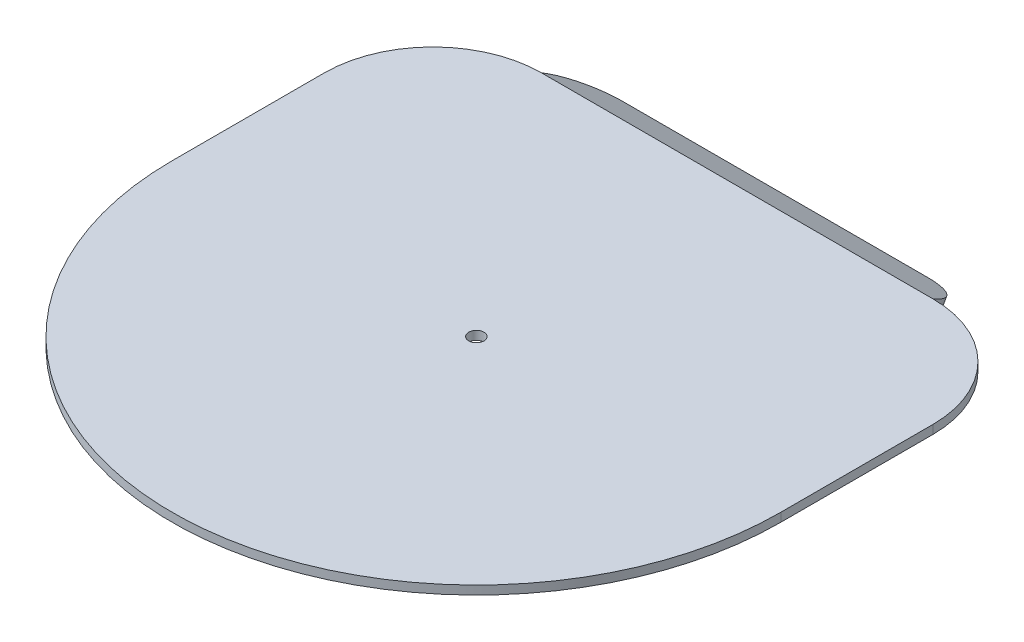
SolidWorks part; units mm, degrees
ref_plane "Front Plane" through (0, 0, 0) normal (0, 0, 1) x (1, 0, 0)
ref_plane "Top Plane" through (0, 0, 0) normal (0, 1, 0) x (1, 0, 0)
ref_plane "Right Plane" through (0, 0, 0) normal (1, 0, 0) x (0, 0, -1)
sketch "Sketch1" plane through (0, 0, 0) normal (0, 1, 0) x (1, 0, 0)
  line L0 (-70, 0) -> (-70, 35)
  line L1 (-45, 60) -> (45, 60)
  line L2 (70, 35) -> (70, 0)
  arc A0 (-70, 0) -> (70, 0) centre (0, 0) ccw
  arc A1 (45, 60) -> (70, 35) centre (45, 35) cw
  arc A2 (-70, 35) -> (-45, 60) centre (-45, 35) cw
  dimension "D1" = 140
  dimension "D3" = 25
  dimension "D2" = 60
extrude "Boss-Extrude1" add sketch "Sketch1" along normal blind 2
sketch "Sketch3" plane through (0, 0, 0) normal (1, 0, 0) x (0, 0, -1)
  line L0 (60, 2) -> (58.8453, 0)
  line L1 (60, 2) -> (68.6603, -3)
  line L2 (58.8453, 0) -> (67.5056, -5)
  line L3 (68.6603, -3) -> (67.5056, -5)
  line L4 (35, 0) -> (60, 0) construction
  line L5 (60, 2) -> (35, 2) construction
  dimension "D1" = 10
  dimension "D2" = 30
extrude "Boss-Extrude2" add sketch "Sketch3" along normal blind 45 and the other way blind 45
fillet "Fillet1" radius 10 2 edges at (-45, -4, -68.0829) (45, -4, -68.0829)
sketch "Sketch4" plane through (0, 2, 0) normal (0, 1, 0) x (1, 0, 0)
  circle A0 centre (0, 0) radius 1.75
  dimension "D1" = 3.5
extrude "Cut-Extrude2" cut sketch "Sketch4" against normal blind 10
sketch "Sketch5" plane through (0, 0, 0) normal (0, -1, 0) x (1, 0, 0)
  circle A0 centre (0, 0) radius 37
  circle A1 centre (0, 0) radius 35
  dimension "D1" = 74
  dimension "D2" = 70
extrude "Boss-Extrude3" add sketch "Sketch5" along normal blind 5
sketch "Sketch6" plane through (0, 0, 0) normal (0, -1, 0) x (1, 0, 0)
  circle A0 centre (0, 0) radius 41
  circle A1 centre (0, 0) radius 43
  dimension "D1" = 82
  dimension "D2" = 86
extrude "Boss-Extrude4" add sketch "Sketch6" along normal blind 5
sketch "Sketch7" plane through (0, 0, 0) normal (0, -1, 0) x (1, 0, 0)
  line L0 (0, -45.4108) -> (0, 0) construction
  line L1 (-4, -49.1795) -> (4, -49.1795)
  line L2 (-4, -49.1795) -> (-4, -41.6421)
  line L3 (-4, -41.6421) -> (4, -41.6421)
  line L4 (4, -49.1795) -> (4, -41.6421)
  line L5 (-4, -49.1795) -> (4, -41.6421) construction
  line L6 (-4, -41.6421) -> (4, -49.1795) construction
  point P0 (0, -45.4108)
  dimension "D1" = 8
extrude "Boss-Extrude5" add sketch "Sketch7" along normal blind 5
sketch "Sketch8" plane through (0, 0, -49.1795) normal (0, 0, -1) x (-1, 0, 0)
  line L0 (0, 0) -> (0, -2.5) construction
  circle A0 centre (0, -2.5) radius 2
  dimension "D1" = 2.5
extrude "Cut-Extrude3" cut sketch "Sketch8" against normal blind 25
pattern_circular "CirPattern1" count 8 every 45 about axis through (0, -5, 0) along (0, -1, 0) of "Cut-Extrude3", "Boss-Extrude5"
